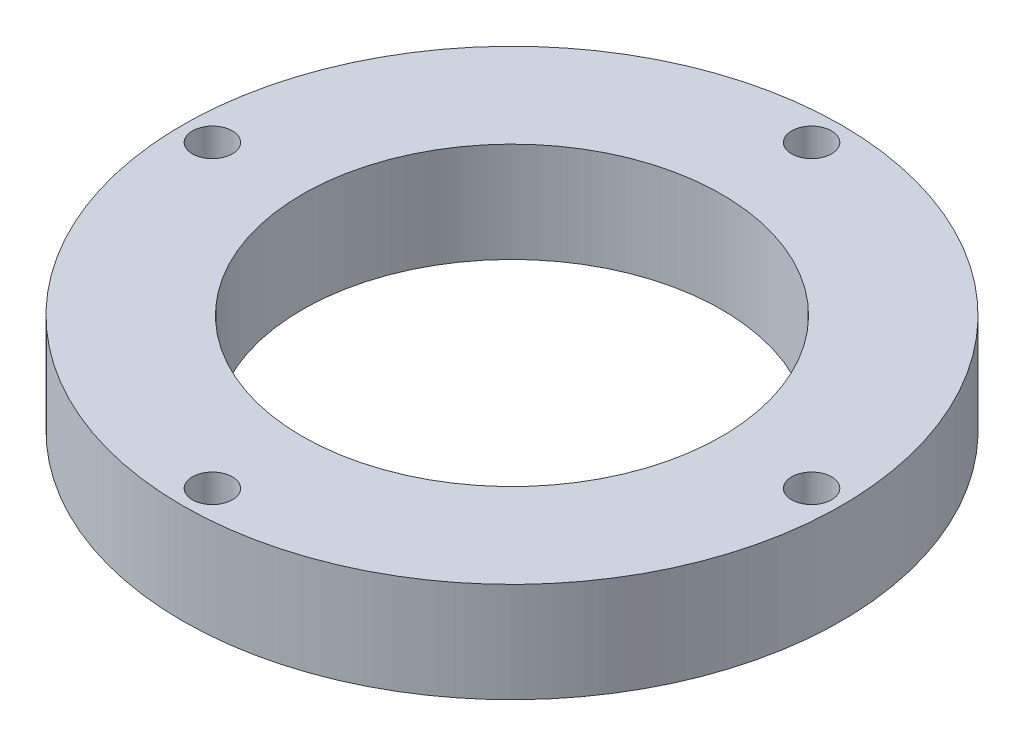
SolidWorks part; units mm, degrees
ref_plane "Front Plane" through (0, 0, 0) normal (0, 0, 1) x (1, 0, 0)
ref_plane "Top Plane" through (0, 0, 0) normal (0, 1, 0) x (1, 0, 0)
ref_plane "Right Plane" through (0, 0, 0) normal (1, 0, 0) x (0, 0, -1)
sketch "Sketch1" plane through (0, 0, 0) normal (0, 1, 0) x (1, 0, 0)
  circle A0 centre (0, 0) radius 41.91
  dimension "D1" = 83.82
extrude "Boss-Extrude1" add sketch "Sketch1" along normal blind 12.7
sketch "Sketch2" plane through (0, 12.7, 0) normal (0, 1, 0) x (1, 0, 0)
  circle A0 centre (0, 0) radius 26.67
  circle A1 centre (0, 0) radius 13.97
  dimension "D1" = 53.34
  dimension "D2" = 27.94
extrude "Cut-Extrude1" cut sketch "Sketch2" against normal up to surface (12.7 mm away) contours A1 region at (0, 12.7, 0) up to face at (0, 0, 41.91)
extrude "Cut-Extrude2" cut sketch "Sketch2<3>" against normal up to surface (12.7 mm away) up to face at (0, 0, 13.97)
sketch "Sketch2<3>" plane through (0, 12.7, 0) normal (0, 1, 0) x (1, 0, 0) same geometry as "Sketch2"
sketch "Sketch3" plane through (0, 12.7, 0) normal (0, 1, 0) x (1, 0, 0)
  circle A0 centre (0, 0) radius 38.1 construction
  circle A1 centre (0, 38.1) radius 2.54
  dimension "D1" = 76.2
  dimension "D2" = 5.08
scale "Scale1" scale about centroid uniform scaling yes scale factor 2
scale "Scale2" bodies to scale 106 scale about centroid uniform scaling yes scale factor 0.5
extrude "Cut-Extrude3" cut sketch "Sketch3" against normal up to surface (12.7 mm away) contours A1 up to face at (0, 0, 26.67)
pattern_circular "CirPattern1" count 4 over 360 about axis through (0, 12.7, 0) along (0, -1, 0) of "Cut-Extrude3"
